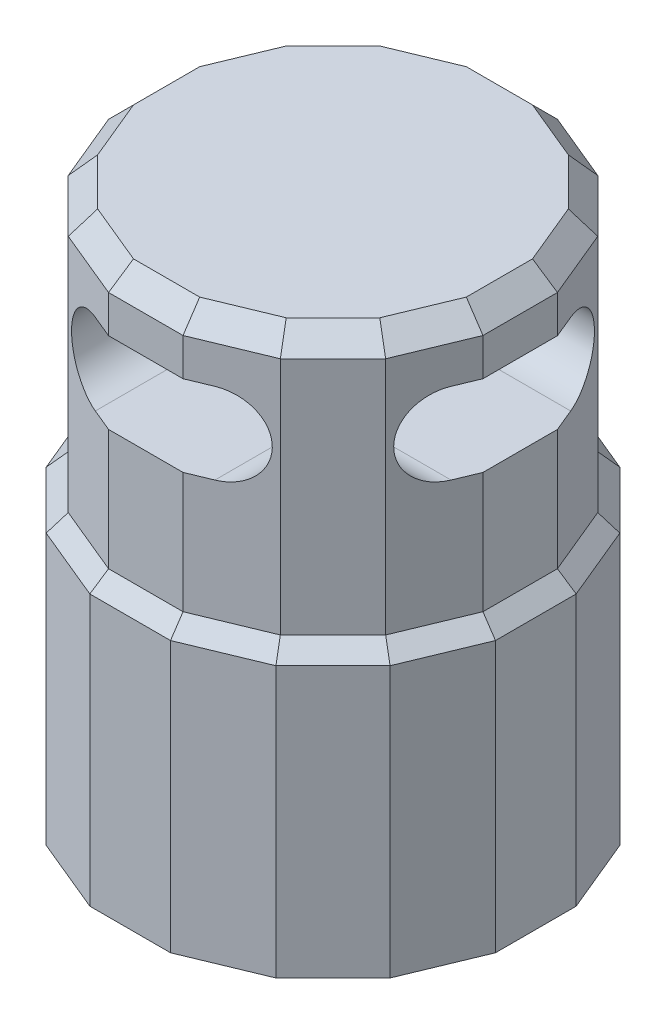
SolidWorks part; units mm, degrees
ref_plane "Front Plane" through (0, 0, 0) normal (0, 0, 1) x (1, 0, 0)
ref_plane "Top Plane" through (0, 0, 0) normal (0, 1, 0) x (1, 0, 0)
ref_plane "Right Plane" through (0, 0, 0) normal (1, 0, 0) x (0, 0, -1)
sketch "Sketch1" plane through (0, 0, 0) normal (0, 1, 0) x (1, 0, 0)
  line L1 (36, 7.1608) -> (30.5193, 20.3924)
  line L2 (30.5193, 20.3924) -> (20.3924, 30.5193)
  line L3 (20.3924, 30.5193) -> (7.1608, 36)
  line L4 (7.1608, 36) -> (-7.1608, 36)
  line L5 (-7.1608, 36) -> (-20.3924, 30.5193)
  line L6 (-20.3924, 30.5193) -> (-30.5193, 20.3924)
  line L7 (-30.5193, 20.3924) -> (-36, 7.1608)
  line L8 (-36, 7.1608) -> (-36, -7.1608)
  line L9 (-36, -7.1608) -> (-30.5193, -20.3924)
  line L10 (-30.5193, -20.3924) -> (-20.3924, -30.5193)
  line L11 (-20.3924, -30.5193) -> (-7.1608, -36)
  line L12 (-7.1608, -36) -> (7.1608, -36)
  line L13 (7.1608, -36) -> (20.3924, -30.5193)
  line L14 (20.3924, -30.5193) -> (30.5193, -20.3924)
  line L15 (30.5193, -20.3924) -> (36, -7.1608)
  line L16 (36, -7.1608) -> (36, 7.1608)
  circle A0 centre (0, 0) radius 36 construction
  dimension "D1" = 72
extrude "Boss-Extrude1" add sketch "Sketch1" along normal blind 50
sketch "Sketch2" plane through (0, 0, 0) normal (0, -1, 0) x (1, 0, 0)
  line L0 (-7.1608, 36) -> (7.1608, 36) construction
  line L1 (33.0626, 22.0917) -> (22.0917, 33.0626)
  line L2 (22.0917, 33.0626) -> (7.7576, 39)
  line L3 (7.7576, 39) -> (-7.7576, 39)
  line L4 (-7.7576, 39) -> (-22.0917, 33.0626)
  line L5 (-22.0917, 33.0626) -> (-33.0626, 22.0917)
  line L6 (-33.0626, 22.0917) -> (-39, 7.7576)
  line L7 (-39, 7.7576) -> (-39, -7.7576)
  line L8 (-39, -7.7576) -> (-33.0626, -22.0917)
  line L9 (-33.0626, -22.0917) -> (-22.0917, -33.0626)
  line L10 (-22.0917, -33.0626) -> (-7.7576, -39)
  line L11 (-7.7576, -39) -> (7.7576, -39)
  line L12 (7.7576, -39) -> (22.0917, -33.0626)
  line L13 (22.0917, -33.0626) -> (33.0626, -22.0917)
  line L14 (33.0626, -22.0917) -> (39, -7.7576)
  line L15 (39, -7.7576) -> (39, 7.7576)
  line L16 (39, 7.7576) -> (33.0626, 22.0917)
  circle A0 centre (0, 0) radius 39 construction
  dimension "D1" = 78
extrude "Boss-Extrude2" add sketch "Sketch2" along normal blind 55
chamfer "Chamfer1" distance 4 angle 45 16 edges at (33.2597, 50, 13.7766) (25.4558, 50, 25.4558) (13.7766, 50, 33.2597) (0, 50, 36) (-13.7766, 50, 33.2597) (-25.4558, 50, 25.4558) (-33.2597, 50, 13.7766) (-36, 50, 0) (-33.2597, 50, -13.7766) (-25.4558, 50, -25.4558) (-13.7766, 50, -33.2597) (0, 50, -36) (13.7766, 50, -33.2597) (25.4558, 50, -25.4558) (33.2597, 50, -13.7766) (36, 50, 0)
chamfer "Chamfer3" distance 3 angle 45 16 edges at (27.5772, 0, 27.5772) (14.9247, 0, 36.0313) (0, 0, 39) (-14.9247, 0, 36.0313) (-27.5772, 0, 27.5772) (-36.0313, 0, 14.9247) (-39, 0, 0) (-36.0313, 0, -14.9247) (-27.5772, 0, -27.5772) (-14.9247, 0, -36.0313) (0, 0, -39) (14.9247, 0, -36.0313) (27.5772, 0, -27.5772) (36.0313, 0, -14.9247) (39, 0, 0) (36.0313, 0, 14.9247)
sketch "Sketch3" plane through (0, 0, 0) normal (0, 0, 1) x (1, 0, 0)
  line L0 (-11.5, 31) -> (11.5, 31) construction
  line L1 (-11.5, 38.8) -> (11.5, 38.8)
  line L2 (-11.5, 23.2) -> (11.5, 23.2)
  line L3 (-6.3652, 50) -> (6.3652, 50) construction
  arc A0 (-11.5, 38.8) -> (-11.5, 23.2) centre (-11.5, 31) ccw
  arc A1 (11.5, 23.2) -> (11.5, 38.8) centre (11.5, 31) ccw
  point P2 (0, 31)
  point P7 (0, 0)
  dimension "D3" = 7.8
  dimension "D1" = 23
  dimension "D2" = 19
extrude "Cut-Extrude1" cut sketch "Sketch3" against normal up to surface and the other way up to surface up to face at (0, 23, -36) other way up to face at (0, 23, 36)
sketch "Sketch4" plane through (0, 0, 0) normal (1, 0, 0) x (0, 0, -1)
  line L0 (-11.5, 31) -> (11.5, 31) construction
  line L1 (-11.5, 38.8) -> (11.5, 38.8)
  line L2 (-11.5, 23.2) -> (11.5, 23.2)
  line L3 (-18.1265, 50) -> (-6.3652, 50) construction
  arc A0 (-11.5, 38.8) -> (-11.5, 23.2) centre (-11.5, 31) ccw
  arc A1 (11.5, 23.2) -> (11.5, 38.8) centre (11.5, 31) ccw
  point P2 (0, 31)
  point P7 (0, 0)
  dimension "D2" = 7.8
  dimension "D1" = 23
  dimension "D3" = 19
extrude "Cut-Extrude2" cut sketch "Sketch4" along normal up to surface and the other way up to surface up to face at (36, 23, 0) other way up to face at (-36, 23, 0)
